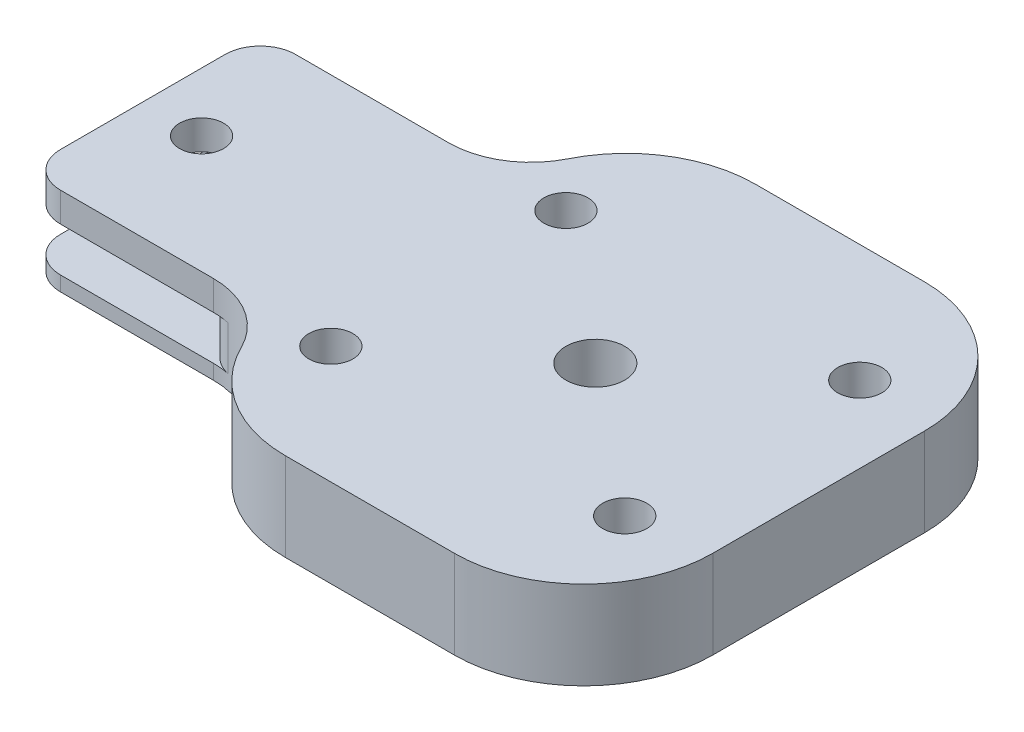
SolidWorks part; units mm, degrees
ref_plane "Front Plane" through (0, 0, 0) normal (0, 0, 1) x (1, 0, 0)
ref_plane "Top Plane" through (0, 0, 0) normal (0, 1, 0) x (1, 0, 0)
ref_plane "Right Plane" through (0, 0, 0) normal (1, 0, 0) x (0, 0, -1)
sketch "Sketch1" plane through (0, 0, 0) normal (1, 0, 0) x (0, 0, -1)
  line L1 (-25.4, -4.7625) -> (25.4, -4.7625)
  line L2 (-25.4, -4.7625) -> (-25.4, 4.7625)
  line L3 (-25.4, 4.7625) -> (25.4, 4.7625)
  line L4 (25.4, -4.7625) -> (25.4, 4.7625)
  line L5 (-25.4, -4.7625) -> (25.4, 4.7625) construction
  line L6 (-25.4, 4.7625) -> (25.4, -4.7625) construction
  point P0 (0, 0)
  dimension "D1" = 50.8
  dimension "D2" = 9.525
extrude "Boss-Extrude1" add sketch "Sketch1" against normal blind 73.025
sketch "Sketch3" plane through (-73.025, 0, 0) normal (-1, 0, 0) x (0, 0, 1)
  line L0 (25.4, -4.7625) -> (-25.4, -4.7625) construction
  line L1 (-6.6675, -3.175) -> (6.6675, -3.175)
  line L2 (-6.6675, -3.175) -> (-6.6675, -0.7937)
  line L4 (6.6675, -3.175) -> (6.6675, -0.7937)
  line L8 (-6.6675, -0.7937) -> (-6.6675, 1.5875)
  line L9 (6.6675, -0.7937) -> (6.6675, 1.5875)
  line L10 (-6.6675, 1.5875) -> (6.6675, 1.5875)
  point P0 (0, -1.9844)
  dimension "D1" = 1.5875
  dimension "D2" = 13.335
  dimension "D3" = 0
  dimension "D4" = 2.3813
  dimension "D5" = 2.3813
extrude "Cut-Extrude2" cut sketch "Sketch3" against normal blind 19.05
sketch "Sketch4" plane through (0, 4.7625, 0) normal (0, 1, 0) x (1, 0, 0)
  line L0 (-73.025, 25.4) -> (-73.025, -25.4) construction
  circle A0 centre (-66.675, 0) radius 2.3813
  dimension "D3" = 4.7625
  dimension "D1" = 6.35
extrude "Cut-Extrude3" cut sketch "Sketch4" against normal through all
sketch "Sketch5" plane through (-73.025, 0, 0) normal (-1, 0, 0) x (0, 0, 1)
  line L1 (-12.7, -4.7625) -> (-25.4, -4.7625)
  line L2 (-12.7, -4.7625) -> (-12.7, 4.7625)
  line L3 (-12.7, 4.7625) -> (-25.4, 4.7625)
  line L4 (-25.4, -4.7625) -> (-25.4, 4.7625)
  line L5 (-12.7, -4.7625) -> (-25.4, 4.7625) construction
  line L6 (-12.7, 4.7625) -> (-25.4, -4.7625) construction
  line L7 (12.7, -4.7625) -> (25.4, -4.7625)
  line L8 (12.7, -4.7625) -> (12.7, 4.7625)
  line L9 (12.7, 4.7625) -> (25.4, 4.7625)
  line L10 (25.4, -4.7625) -> (25.4, 4.7625)
  line L11 (12.7, -4.7625) -> (25.4, 4.7625) construction
  line L12 (12.7, 4.7625) -> (25.4, -4.7625) construction
  point P0 (-19.05, 0)
  point P6 (19.05, 0)
  dimension "D1" = 12.7
  dimension "D2" = 12.7
extrude "Cut-Extrude4" cut sketch "Sketch5" against normal blind 29.21
fillet "Fillet2" radius 8.89 2 edges at (-43.815, 0, 12.7) (-43.815, 0, -12.7)
fillet "Fillet3" radius 3.81 1 edges at (-73.025, 0, -12.7)
fillet "Fillet4" radius 13.97 2 edges at (-43.815, 0, 25.4) (-43.815, 0, -25.4)
fillet "Fillet5" radius 13.97 2 edges at (0, 0, -25.4) (0, 0, 25.4)
sketch "Sketch13" plane through (0, -4.7625, 0) normal (0, -1, 0) x (1, 0, 0)
  line L0 (-24.13, 21.4313) -> (-24.13, -21.4313) construction
  line L1 (-30.48, 6.35) -> (-30.48, 15.0812)
  line L2 (-17.78, 6.35) -> (-17.78, 15.0813)
  line L3 (-17.78, 6.35) -> (-8.255, 6.35)
  line L4 (-30.48, -15.0812) -> (-30.48, -6.35)
  line L5 (-18.6906, 6.35) -> (-17.78, 6.35) construction
  line L6 (-17.78, -15.0812) -> (-17.78, -6.35)
  line L7 (-40.005, -6.35) -> (-30.48, -6.35)
  line L8 (-29.5694, -18.3578) -> (-18.6906, 18.3578) construction
  line L9 (-40.005, 6.35) -> (-30.48, 6.35)
  line L10 (-46.355, 0) -> (-1.905, 0) construction
  line L11 (-43.2448, -5.4614) -> (-5.0152, 5.4614) construction
  line L12 (-43.2448, 5.4614) -> (-5.0152, -5.4614) construction
  line L13 (-29.5694, 18.3578) -> (-18.6906, -18.3578) construction
  line L14 (-17.78, -6.35) -> (-8.255, -6.35)
  line L15 (-17.78, 6.35) -> (-17.6942, 6.254) construction
  arc A0 (-17.78, 15.0813) -> (-30.48, 15.0812) centre (-24.13, 15.0812) ccw
  arc A1 (-8.255, -6.35) -> (-8.255, 6.35) centre (-8.255, 0) ccw
  arc A2 (-30.48, -15.0812) -> (-17.78, -15.0812) centre (-24.13, -15.0812) ccw
  arc A3 (-40.005, 6.35) -> (-40.005, -6.35) centre (-40.005, 0) ccw
  point P0 (-24.13, 0)
  point P1 (-24.13, 0)
  point P5 (-24.13, 0)
  dimension "D7" = 12.7
  dimension "D10" = 12.7
  dimension "D4" = 12.7
  dimension "D8" = 12.7
  dimension "D2" = 12.7
  dimension "D3" = 12.7
extrude "Cut-Extrude10" cut sketch "Sketch13" against normal blind 3.175 contours L9 A3 L7 L14 A1 L3 region at (-24.13, -4.7625, 0)
sketch "Sketch14" plane through (0, -1.5875, 0) normal (0, -1, 0) x (1, 0, 0)
  line L0 (-24.13, 21.4313) -> (-24.13, -21.4313) construction
  line L1 (-46.355, 0) -> (-1.905, 0) construction
  circle A0 centre (-24.13, 0) radius 3.175
  arc A2 (-17.78, 15.0813) -> (-30.48, 15.0812) centre (-24.13, 15.0812) ccw construction
  arc A3 (-30.48, -15.0812) -> (-17.78, -15.0812) centre (-24.13, -15.0812) ccw construction
  arc A4 (-40.005, 6.35) -> (-40.005, -6.35) centre (-40.005, 0) ccw construction
  arc A5 (-8.255, -6.35) -> (-8.255, 6.35) centre (-8.255, 0) ccw construction
  dimension "D1" = 6.35
extrude "Cut-Extrude11" cut sketch "Sketch14" against normal through all
sketch "Sketch17" plane through (0, -4.7625, 0) normal (0, -1, 0) x (-1, 0, 0)
  circle A0 centre (40.005, -12.7) radius 2.3812
  circle A1 centre (40.005, 12.7) radius 2.3812
  circle A2 centre (8.255, -12.7) radius 2.3813
  circle A3 centre (8.255, 12.7) radius 2.3813
  dimension "D1" = 4.7625
  dimension "D2" = 4.7625
  dimension "D5" = 4.7625
  dimension "D7" = 4.7625
  dimension "D3" = 6.35
  dimension "D4" = 6.35
  dimension "D6" = 6.35
  dimension "D8" = 6.35
extrude "Cut-Extrude12" cut sketch "Sketch17" against normal through all
sketch "Sketch19" plane through (0, 0, 12.7) normal (0, 0, 1) x (1, 0, 0)
  line L0 (-73.025, -3.175) -> (-73.025, 1.5875)
  line L1 (-73.025, -3.175) -> (-53.975, -3.175)
  line L2 (-73.025, 1.5875) -> (-53.975, 1.5875)
  line L3 (-53.975, -3.175) -> (-53.975, 1.5875)
  dimension "D1" = 19.05
extrude "Cut-Extrude14" cut sketch "Sketch19" against normal up to surface (6.0325 mm away) up to face at (-63.5, -0.7937, 6.6675)
fillet "Fillet8" radius 3.81 1 edges at (-53.975, -0.7937, 12.7)
fillet "Fillet9" radius 3.81 2 edges at (-73.025, -3.9688, 12.7) (-73.025, 3.175, 12.7)
